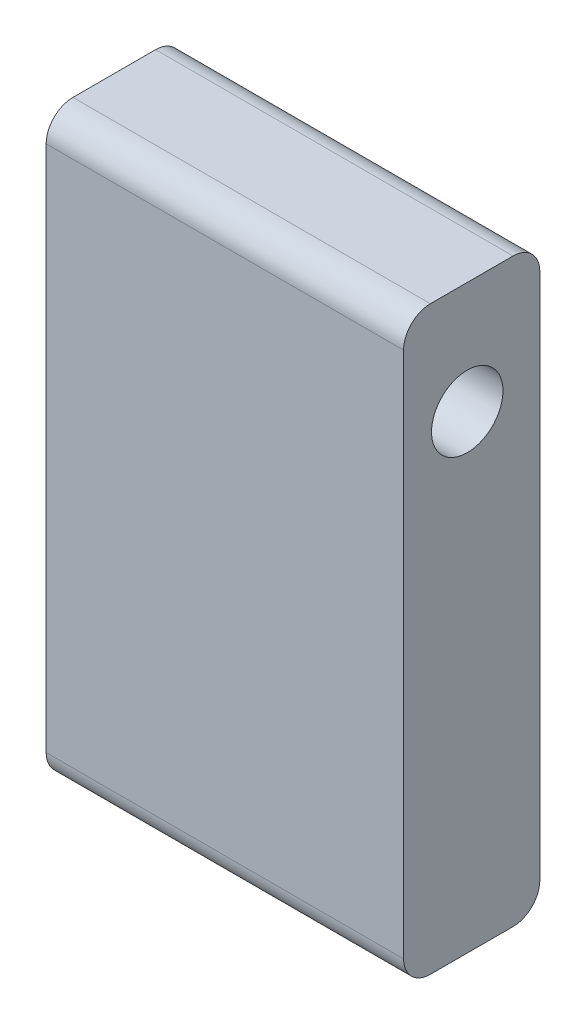
SolidWorks part; units mm, degrees
material "ABS"
ref_plane "Front Plane" through (0, 0, 0) normal (0, 0, 1) x (1, 0, 0)
ref_plane "Top Plane" through (0, 0, 0) normal (0, 1, 0) x (1, 0, 0)
ref_plane "Right Plane" through (0, 0, 0) normal (1, 0, 0) x (0, 0, -1)
sketch "Sketch1" plane through (0, 0, 0) normal (1, 0, 0) x (0, 0, -1)
  line L0 (0, 0) -> (0, 16) construction
  line L2 (-3.25, -5) -> (3.25, -5)
  line L3 (-3.25, -5) -> (-3.25, 21)
  line L4 (-3.25, 21) -> (3.25, 21)
  line L5 (3.25, -5) -> (3.25, 21)
  line L6 (0, 21) -> (0, -5) construction
  line L7 (-3.25, 8) -> (3.25, 8) construction
  circle A0 centre (0, 0) radius 1.6 construction
  circle A1 centre (0, 16) radius 1.6
  circle A2 centre (0, 16) radius 2.8
  circle A3 centre (0, 0) radius 2.8 construction
  circle A4 centre (0, 5) radius 2.55
  point P5 (0, 8)
  point P13 (-1.2031, 5)
  point P14 (0, 5)
  dimension "D1" = 3.2
  dimension "D5" = 5.6
  dimension "D6" = 5.1
  dimension "D7" = 11
  dimension "D2" = 16
  dimension "D3" = 6.5
  dimension "D4" = 26
extrude "Boss-Extrude1" add sketch "Sketch1" against normal blind 16 contours L2 L5 L4 L3 A3 A2 | L5 A4 region at (0, 8, 2.982) region at (0, 5, 0)
extrude "Boss-Extrude3" add sketch "Sketch1<3>" against normal blind 5 contours A2 A1 | A3 A0 region at (0, 16, 2.7208)
sketch "Sketch1<3>" plane through (0, 0, 0) normal (1, 0, 0) x (0, 0, -1) same geometry as "Sketch1"
extrude "Cut-Extrude2" cut sketch "Sketch1<4>" along normal blind 8.4 from surface contours A4 starting at face at (-16, 16, -2.8)
sketch "Sketch1<4>" plane through (0, 0, 0) normal (1, 0, 0) x (0, 0, -1) same geometry as "Sketch1"
sketch "Sketch2" plane through (0, 0, 0) normal (0, 0, 1) x (1, 0, 0)
  circle A0 centre (0, 0) radius 50
  dimension "D1" = 100
extrude "Cut-Extrude1" cut sketch "Sketch2" against normal blind 0.4 from surface starting at face at (-8, 8, 3.25)
fillet "Fillet1" radius 1.2 4 edges at (-8, -5, 2.85) (-8, -5, -3.25) (-8, 21, -3.25) (-8, 21, 2.85)
